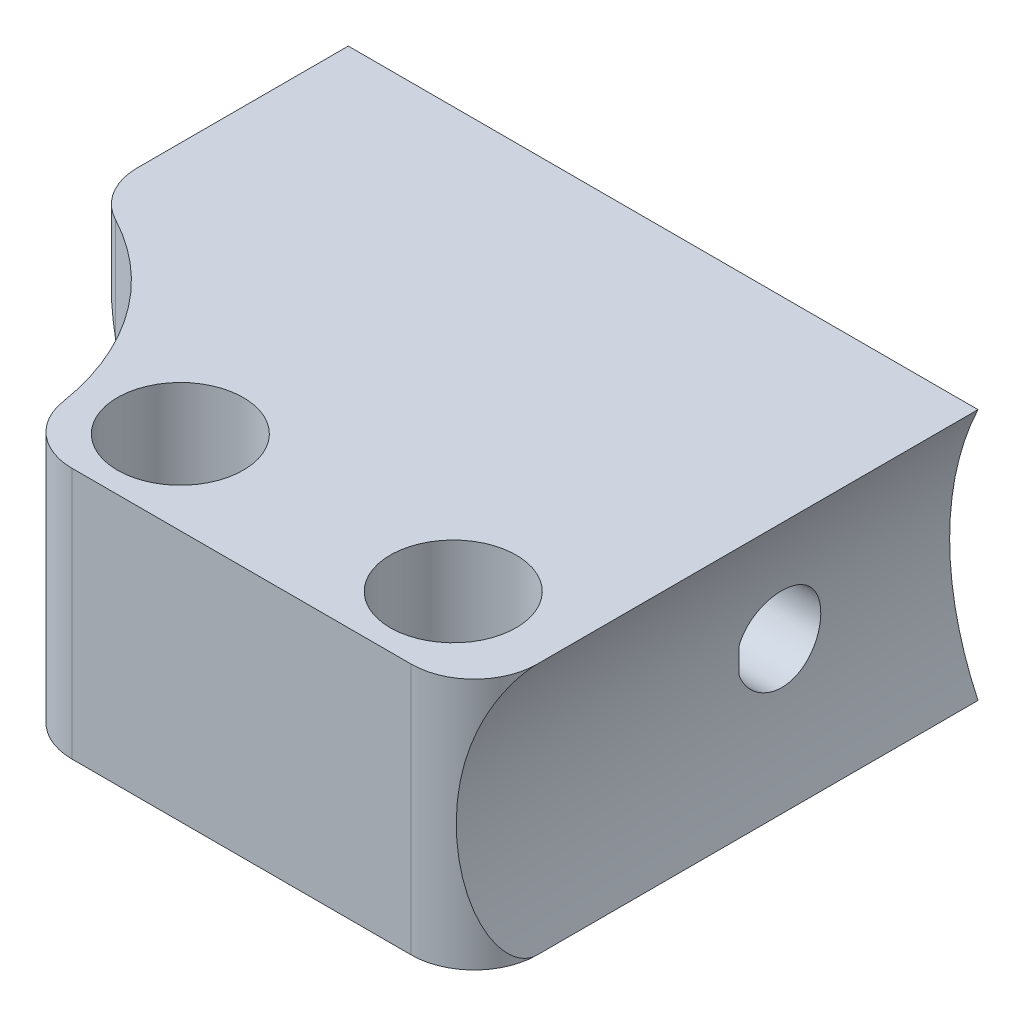
SolidWorks part; units mm, degrees
ref_plane "前视基准面" through (0, 0, 0) normal (0, 0, 1) x (1, 0, 0)
ref_plane "上视基准面" through (0, 0, 0) normal (0, 1, 0) x (1, 0, 0)
ref_plane "右视基准面" through (0, 0, 0) normal (1, 0, 0) x (0, 0, -1)
other "Configuration Table"
sketch "草图1" plane through (0, 0, 0) normal (0, 1, 0) x (1, 0, 0)
  line L1 (-15, 12) -> (15, 12)
  line L2 (-15, 12) -> (-15, 0)
  line L3 (-7, -12) -> (15, -12)
  line L4 (15, 12) -> (15, -12)
  line L5 (-15, 12) -> (15, -12) construction
  line L6 (-8.0265, -6.4212) -> (15, 12) construction
  arc A0 (-15, 0) -> (-7, -12) centre (-18.9807, -11.3205) cw
  circle A1 centre (10, -8) radius 3
  circle A2 centre (-3, -8) radius 3
  point P0 (0, 0)
  point P13 (0, 0)
  dimension "D4" = 12
  dimension "D7" = 6
  dimension "D1" = 30
  dimension "D2" = 24
  dimension "D3" = 8
  dimension "D5" = 12
  dimension "D6" = 5
  dimension "D8" = 13
extrude "凸台-拉伸1" add sketch "草图1" along normal blind 12
fillet "圆角1" radius 3 2 edges at (-7, 6, 12) (-15, 6, 0)
fillet "圆角2" radius 3 1 edges at (15, 6, 12)
sketch "草图2" plane through (-15, 0, 0) normal (-1, 0, 0) x (0, 0, 1)
  line L0 (-1.9561, 6) -> (-14.978, 6) construction
  line L1 (-1.9561, 0) -> (-1.9561, 12) construction
  line L2 (-6.3287, 10) -> (-6.3287, 2)
  line L3 (-6.3287, 2) -> (-12, 3)
  line L4 (-12, 12) -> (-12, 0) construction
  line L5 (-12, 3) -> (-12, 9)
  line L6 (-12, 9) -> (-6.3287, 10)
  arc A0 (-6.3287, 10) -> (-6.3287, 2) centre (-3.8609, 6) cw
  circle A1 centre (-3.8609, 6) radius 2
  line M7 (-1.9561, 0) -> (-1.9561, 12)
  line M9 (-12, 12) -> (-12, 0)
  dimension "D4" = 4.7
  dimension "D5" = 4
  dimension "D1" = 6
  dimension "D2" = 8
  dimension "D3" = 80
extrude "切除-拉伸1" cut sketch "草图2" against normal blind 23 contours L0 L2 L6 M9 | L2 L0 L5 L3 region at (-15, 4.2381, -9.0293) region at (-15, 7.7619, -9.0293)
extrude "切除-拉伸2" cut sketch "草图2<3>" against normal through all contours L0 A1 M7 | L0 A1 M7 region at (-15, 5.1473, -3.873) region at (-15, 6.8527, -3.873)
sketch "草图2<3>" plane through (-15, 0, 0) normal (-1, 0, 0) x (0, 0, 1) same geometry as "草图2"
extrude "切除-拉伸3" cut sketch "草图2<4>" against normal blind 3 contours A1 L0 L2 A0 M7 | L0 A1 A0 L2 M7 | A1 A0 M7 region at (-15, 3.0874, -4.2338) region at (-15, 8.9126, -4.2338) region at (-15, 6, -0.7985)
sketch "草图2<4>" plane through (-15, 0, 0) normal (-1, 0, 0) x (0, 0, 1) same geometry as "草图2"
sketch "草图4" plane through (0, 0, -12) normal (0, 0, -1) x (-1, 0, 0)
  arc A0 (-15, 12) -> (-15, 0) centre (-27.6491, 6) cw
  dimension "D1" = 14
extrude "切除-拉伸8" cut sketch "草图4" against normal through all and the other way through all flip side to cut
